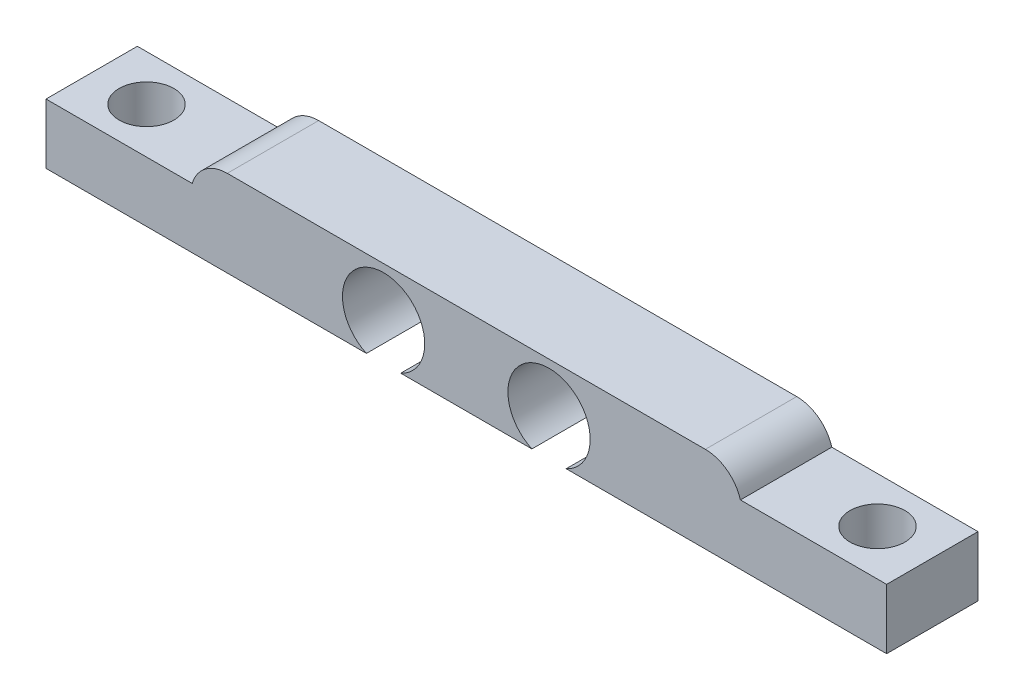
SolidWorks part; units mm, degrees
ref_plane "Plan de face" through (0, 0, 0) normal (0, 0, 1) x (1, 0, 0)
ref_plane "Plan de dessus" through (0, 0, 0) normal (0, 1, 0) x (1, 0, 0)
ref_plane "Plan de droite" through (0, 0, 0) normal (1, 0, 0) x (0, 0, -1)
sketch "Sketch1" plane through (0, 0, 0) normal (0, 0, 1) x (1, 0, 0)
  line L1 (0, 0) -> (20, 0)
  line L2 (0, 0) -> (0, -2.2727)
  line L3 (0, -2.2727) -> (20, -2.2727)
  line L4 (20, 0) -> (20, -2.2727)
  line L5 (-5, 0) -> (25, 0)
  line L6 (-5, 0) -> (-5, 4.7273)
  line L7 (-5, 4.7273) -> (25, 4.7273)
  line L8 (25, 0) -> (25, 4.7273)
  line L9 (20, 0) -> (33, 0)
  line L10 (20, 0) -> (20, 3.288)
  line L11 (20, 3.288) -> (33, 3.288)
  line L12 (33, 0) -> (33, 3.288)
  line L13 (0, 0) -> (-13, 0)
  line L14 (0, 0) -> (0, 3.288)
  line L15 (0, 3.288) -> (-13, 3.288)
  line L16 (-13, 0) -> (-13, 3.288)
  dimension "D2" = 20
  dimension "D3" = 30
  dimension "D4" = 7
  dimension "D5" = 5
  dimension "D7" = 13
  dimension "D8" = 13
extrude "Boss-Extrude1" add sketch "Sketch1" against normal blind 5 contours L15 L2 L3 L4 L11 L8 L7 L6 | L2 L15 L6 L5 | L16 L13 L6 L15 | L11 L4 L5 L8 | L9 L12 L11 L8 region at (10, 2.5808, 0) region at (-2.5, 1.644, 0) region at (22.5, 1.644, 0) region at (-9, 1.644, 0) region at (29, 1.644, 0)
fillet "Fillet1" radius 2 2 edges at (-5, 4.7273, -2.5) (25, 4.7273, -2.5)
sketch "Sketch2" plane through (0, 3.288, 0) normal (0, 1, 0) x (1, 0, 0)
  line L0 (-13, 5) -> (-13, 0) construction
  circle A0 centre (-10, 2.5) radius 1.5
  circle A1 centre (30, 2.5) radius 1.5
  dimension "D1" = 3
  dimension "D2" = 3
  dimension "D3" = 3
  dimension "D5" = 40
extrude "Cut-Extrude1" cut sketch "Sketch2" against normal through all both and the other way through all
sketch "Sketch3" plane through (0, 0, 0) normal (0, 0, 1) x (1, 0, 0)
  line L1 (10, 4.7273) -> (10, 39.7) construction
  line L2 (-3.0802, 4.7273) -> (23.0802, 4.7273) construction
  circle A0 centre (14.5271, 2.0452) radius 2.25
  circle A1 centre (5.4729, 2.0452) radius 2.25
  dimension "D1" = 4.5
extrude "Cut-Extrude2" cut sketch "Sketch3" against normal through all both and the other way through all
